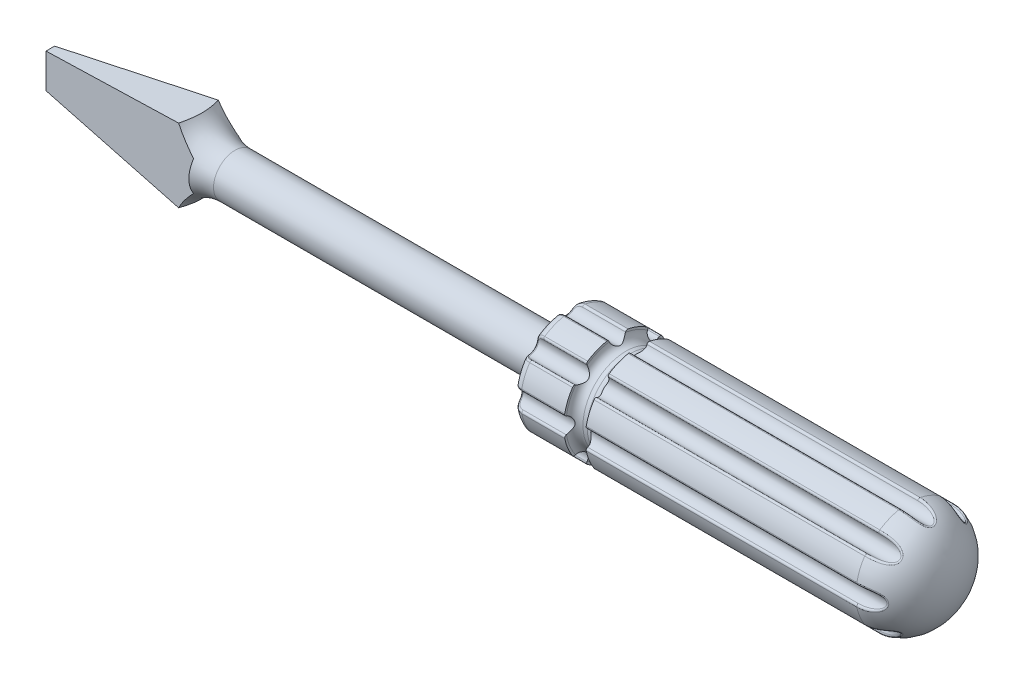
SolidWorks part; units mm, degrees
material "1023 Carbon Steel Sheet (SS)"
ref_plane "Front Plane" through (0, 0, 0) normal (0, 0, 1) x (1, 0, 0)
ref_plane "Top Plane" through (0, 0, 0) normal (0, 1, 0) x (1, 0, 0)
ref_plane "Right Plane" through (0, 0, 0) normal (1, 0, 0) x (0, 0, -1)
sketch "Sketch1" plane through (0, 0, 0) normal (0, 0, 1) x (1, 0, 0)
  line L0 (0, 0) -> (6767.5962, 0) construction
  line L1 (0.9301, 0) -> (-6766.6661, 0) construction
  line L2 (0, 0) -> (0, 6767.5962) construction
  line L3 (0, 0) -> (0, 6.25)
  line L4 (0, 6.25) -> (6, 6.25)
  line L5 (6, 6.25) -> (6, 5)
  line L6 (6, 5) -> (8.5, 5)
  line L7 (8.5, 5) -> (8.5, 6.25)
  line L8 (8.5, 6.25) -> (40, 6.25)
  line L9 (0, 0) -> (45, 0)
  ellipse E0 centre (40, 0) end of major axis (40, -6.25) minor radius 5 (45, 0) -> (40, 6.25) ccw
  point P15 (0, 0)
  dimension "D1" = 12.5
  dimension "D2" = 10
  dimension "D3" = 6
  dimension "D4" = 5
  dimension "D5" = 12.5
  dimension "D6" = 2.5
  dimension "D7" = 45
revolve "Revolve2" add sketch "Sketch1" angle 360 about L0
sketch "Sketch2" plane through (0, 0, 0) normal (-1, 0, 0) x (0, 0, 1)
  circle A0 centre (0, 0) radius 2.5
  dimension "D1" = 5
extrude "Boss-Extrude1" add sketch "Sketch2" along normal blind 43.5
sketch "Sketch3" plane through (0, 0, 0) normal (0, 0, 1) x (1, 0, 0)
  line L0 (0, 0) -> (50000, 0) construction
  line L1 (-43.5, 2.5) -> (-43.5, -2.5) construction
  line L2 (-43.5, 8.25) -> (-60, 8.25)
  line L3 (-43.5, 8.25) -> (-43.5, -8.25)
  line L4 (-43.5, -8.25) -> (-60, -8.25)
  line L5 (-60, 8.25) -> (-60, -8.25)
  dimension "D1" = 16.5
extrude "Boss-Extrude2" add sketch "Sketch3" along normal mid plane 16.5
fillet "Fillet1" radius 5 1 edges at (-43.5, 0, 2.5)
sketch "Sketch4" plane through (0, 0, 8.25) normal (0, 0, 1) x (1, 0, 0)
  line L0 (-60, 0) -> (49940, 0) construction
  line L1 (-60, 8.25) -> (-60, -8.25) construction
  line L2 (-60, 2) -> (-39.9814, 4.6355)
  line L3 (-39.9814, 4.6355) -> (-39.9814, 8.25)
  line L4 (-39.9814, 8.25) -> (-60, 8.25)
  line L5 (-60, 8.25) -> (-60, 2)
  line L6 (-39.9814, -8.25) -> (-60, -8.25)
  line L7 (-39.9814, -4.6355) -> (-39.9814, -8.25)
  line L8 (-60, -2) -> (-39.9814, -4.6355)
  line L9 (-60, -8.25) -> (-60, -2)
  line L10 (-43.5, 8.25) -> (-60, 8.25) construction
  point P4 (-60, 0)
  dimension "D1" = 15
  dimension "D2" = 4
extrude "Cut-Extrude7" cut sketch "Sketch4" against normal up to next contours L5 L2 L3 L4 | L6 L9 L8 L7
sketch "Sketch8" plane through (0, 0, 0) normal (0, 1, 0) x (1, 0, 0)
  line L0 (-60, 0) -> (49940, 0) construction
  line L1 (-60, 8.25) -> (-60, -8.25) construction
  line L2 (-60, 0.5) -> (-40.8093, 2.517)
  line L4 (-43.5, 8.25) -> (-60, 8.25)
  line L5 (-60, 8.25) -> (-60, 0.5)
  line L6 (-43.5, -8.25) -> (-60, -8.25)
  line L8 (-60, -0.5) -> (-40.8093, -2.517)
  line L9 (-60, -8.25) -> (-60, -0.5)
  line L11 (-60, 8.25) -> (-43.5, 8.25) construction
  line L12 (-40.8093, 8.273) -> (-40.8093, 2.517)
  line L13 (-40.8093, -2.517) -> (-40.8093, -8.25)
  line L15 (-43.5, 8.25) -> (-40.8093, 8.273)
  line L16 (-43.5, -8.25) -> (-40.8093, -8.25)
  point P4 (-60, 0)
  dimension "D1" = 12
  dimension "D2" = 1
extrude "Cut-Extrude9" cut sketch "Sketch8" against normal up to next and the other way blind 16.5
fillet "Fillet3" radius 1 3 edges at (8.5, 0, 5) (6, 0, 5) (0, 0, 6.25)
sketch "Sketch9" plane through (0, 0, 0) normal (-1, 0, 0) x (0, 0, 1)
  circle A0 centre (0, 6.25) radius 1
  circle A1 centre (0, 0) radius 6.25 construction
  point P2 (0, 6.25)
  point P6 (0, 0)
  dimension "D1" = 2
extrude "Cut-Extrude10" cut sketch "Sketch9" against normal through all
fillet "Fillet4" radius 0.25 7 edges at (0.1628, 5.7334, -0.8562) (0.1646, 5.7359, 0.8577) (42.7123, 5.2504, -0.0283) (3.5, 6.17, -0.9968) (3.5, 6.17, 0.9968) (24.25, 6.17, -0.9968) (24.25, 6.17, 0.9968)
pattern_circular "CirPattern1" count 8 over 360 about axis through (-43.5, 0, 0) along (1, 0, 0) of "Cut-Extrude10", "Fillet4" reverse direction yes
